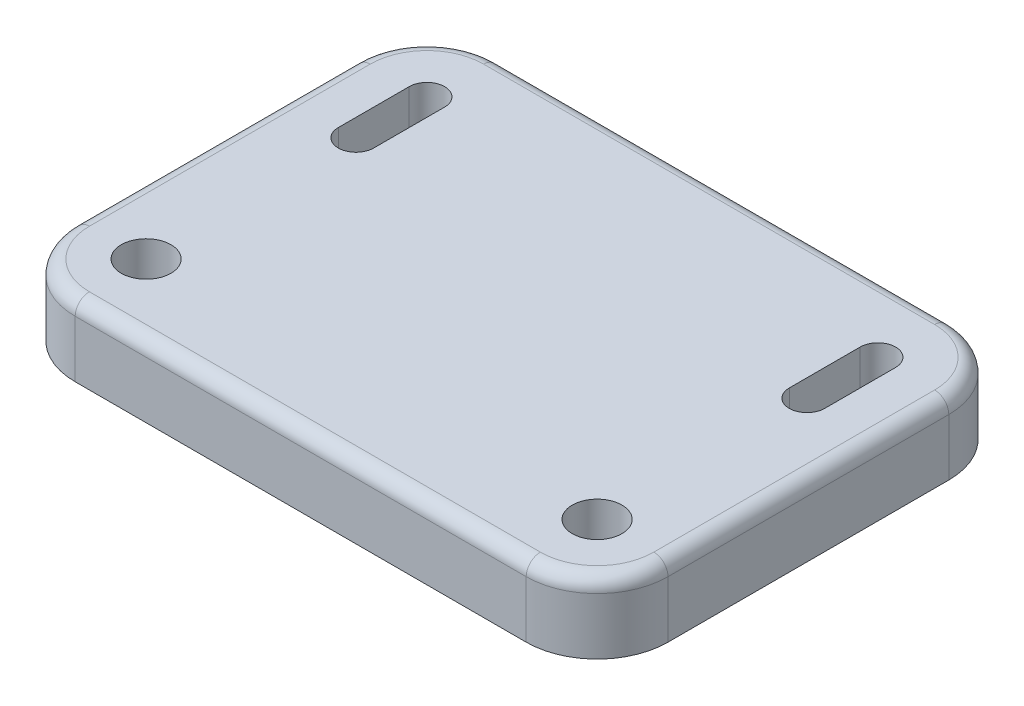
SolidWorks part; units mm, degrees
ref_plane "Front Plane" through (0, 0, 0) normal (0, 0, 1) x (1, 0, 0)
ref_plane "Top Plane" through (0, 0, 0) normal (0, 1, 0) x (1, 0, 0)
ref_plane "Right Plane" through (0, 0, 0) normal (1, 0, 0) x (0, 0, -1)
sketch "Sketch1" plane through (0, 0, 0) normal (0, 1, 0) x (1, 0, 0)
  line L0 (5, 19.8) -> (5, 24.8) construction
  line L1 (0, 0) -> (41.8, 0)
  line L2 (0, 0) -> (0, 29.8)
  line L3 (0, 29.8) -> (41.8, 29.8)
  line L4 (41.8, 0) -> (41.8, 29.8)
  line L5 (5, 19.8) -> (36.8, 19.8) construction
  line L6 (5, 19.8) -> (5, 5) construction
  line L7 (5, 5) -> (36.8, 5) construction
  line L8 (36.8, 19.8) -> (36.8, 5) construction
  line L9 (3.75, 19.8) -> (3.75, 24.8)
  line L10 (6.25, 19.8) -> (6.25, 24.8)
  line L11 (36.8, 19.8) -> (36.8, 24.8) construction
  line L12 (35.55, 19.8) -> (35.55, 24.8)
  line L13 (38.05, 19.8) -> (38.05, 24.8)
  line L14 (0, 0) -> (5, 5) construction
  line L15 (36.8, 5) -> (41.8, 0) construction
  circle A0 centre (5, 5) radius 1.75
  circle A1 centre (36.8, 5) radius 1.75
  arc A2 (3.75, 19.8) -> (6.25, 19.8) centre (5, 19.8) ccw
  arc A3 (6.25, 24.8) -> (3.75, 24.8) centre (5, 24.8) ccw
  arc A4 (35.55, 19.8) -> (38.05, 19.8) centre (36.8, 19.8) ccw
  arc A5 (38.05, 24.8) -> (35.55, 24.8) centre (36.8, 24.8) ccw
  point P11 (5, 22.3)
  point P17 (36.8, 22.3)
  dimension "D1" = 1.25
  dimension "D2" = 3.5
  dimension "D3" = 31.8
  dimension "D4" = 14.8
  dimension "D5" = 5
  dimension "D6" = 5
  dimension "D7" = 5
  dimension "D8" = 5
extrude "Boss-Extrude1" add sketch "Sketch1" along normal blind 5
fillet "Fillet1" radius 5 4 edges at (0, 2.5, -29.8) (41.8, 2.5, -29.8) (41.8, 2.5, 0) (0, 2.5, 0)
fillet "Fillet2" radius 1 8 edges at (1.4645, 5, -1.4645) (0, 5, -14.9) (1.4645, 5, -28.3355) (20.9, 5, -29.8) (40.3355, 5, -28.3355) (41.8, 5, -14.9) (40.3355, 5, -1.4645) (20.9, 5, 0)
